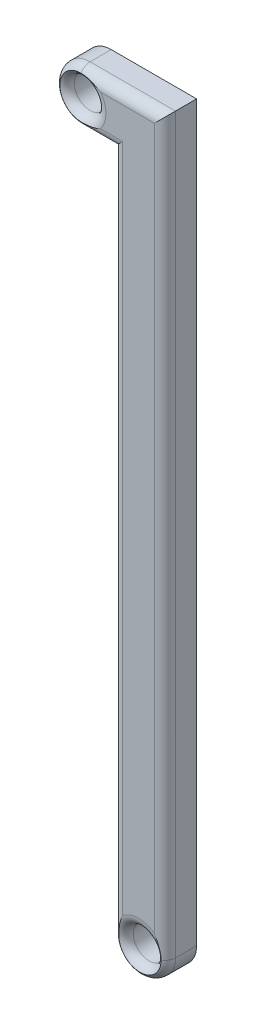
SolidWorks part; units mm, degrees
ref_plane "Front Plane" through (0, 0, 0) normal (0, 0, 1) x (1, 0, 0)
ref_plane "Top Plane" through (0, 0, 0) normal (0, 1, 0) x (1, 0, 0)
ref_plane "Right Plane" through (0, 0, 0) normal (1, 0, 0) x (0, 0, -1)
sketch "Sketch1" plane through (0, 0, 0) normal (0, 0, 1) x (1, 0, 0)
  line L0 (3.2312, -1.9999) -> (8.8212, -1.9999) construction
  line L1 (8.8212, -1.9999) -> (8.8212, -68.9999) construction
  line L2 (3.2312, -4.4999) -> (6.3212, -4.4999)
  line L3 (6.3212, -4.4999) -> (6.3212, -68.9999)
  line L4 (3.2312, 0.5001) -> (11.3212, 0.5001)
  line L5 (11.3212, 0.5001) -> (11.3212, -68.9999)
  circle A0 centre (3.2312, -1.9999) radius 1.5
  circle A1 centre (8.8212, -68.9999) radius 1.5
  arc A2 (3.2312, -4.4999) -> (3.2312, 0.5001) centre (3.2312, -1.9999) cw
  arc A3 (6.3212, -68.9999) -> (11.3212, -68.9999) centre (8.8212, -68.9999) ccw
  dimension "D3" = 3
  dimension "D4" = 3
  dimension "D1" = 5.59
  dimension "D2" = 67
  dimension "D5" = 2.5
  dimension "D6" = 2.5
extrude "Boss-Extrude1" add sketch "Sketch1" along normal blind 3
fillet "Fillet1" radius 1 8 edges at (10.3212, -68.9999, 3) (4.7312, -1.9999, 3) (7.2762, 0.5001, 3) (11.3212, -34.2499, 3) (8.8212, -71.4999, 3) (6.3212, -36.7499, 3) (4.7762, -4.4999, 3) (0.7312, -1.9999, 3)
